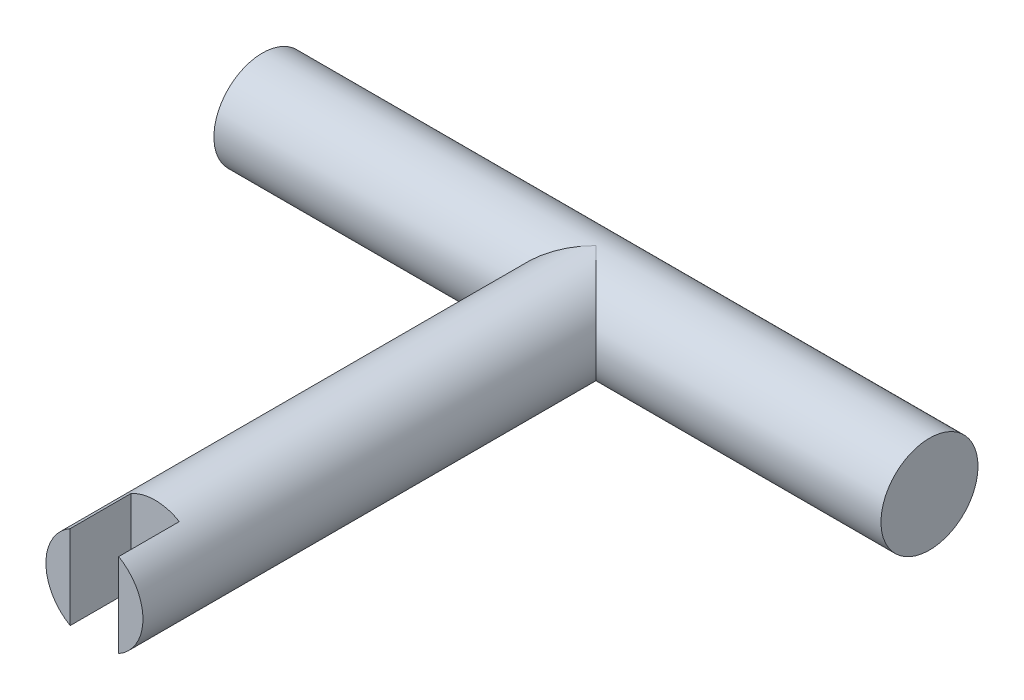
SolidWorks part; units mm, degrees
ref_plane "Front Plane" through (0, 0, 0) normal (0, 0, 1) x (1, 0, 0)
ref_plane "Top Plane" through (0, 0, 0) normal (0, 1, 0) x (1, 0, 0)
ref_plane "Right Plane" through (0, 0, 0) normal (1, 0, 0) x (0, 0, -1)
sketch "LAYOUT" plane through (0, 0, 0) normal (0, 1, 0) x (1, 0, 0)
  line L0 (0, 0) -> (0, 141.5) construction
  line L1 (-18.6718, 141.5) -> (18.6718, 141.5) construction
  line L2 (0, 141.5) -> (0, 161.0961) construction
  line L3 (-15.8007, 105.15) -> (14.7476, 105.15) construction
  line L4 (-27.3866, 200) -> (27.4888, 200) construction
  point P7 (0, 141.5)
  dimension "D1" = 141.5
  dimension "D2" = 105.15
  dimension "D3" = 200
ref_axis "Axis1" through (0, 0, -169.1509) along (0, 0, 1)
ref_plane "Plane1" through (0, 0, -105.15) normal (0, 0, 1) x (1, 0, 0)
sketch "Sketch1" plane through (0, 0, -105.15) normal (0, 0, 1) x (1, 0, 0)
  circle A0 centre (0, 0) radius 4
  dimension "D1" = 8
extrude "Boss-Extrude2" add sketch "Sketch1" against normal up to vertex (36.35 mm away) up to point (0, 0, -141.5)
sketch "Sketch2" plane through (0, 0, -105.15) normal (0, 0, 1) x (1, 0, 0)
  line L0 (-2, 3.4641) -> (-2, -3.4641)
  line L1 (2, 3.4641) -> (2, -3.4641)
  circle A0 centre (0, 0) radius 4 construction
  arc A1 (2, -3.4641) -> (2, 3.4641) centre (0, 0) ccw
  arc A2 (-2, -3.4641) -> (2, -3.4641) centre (0, 0) ccw construction
  arc A3 (2, 3.4641) -> (-2, 3.4641) centre (0, 0) ccw construction
  arc A4 (-2, 3.4641) -> (-2, -3.4641) centre (0, 0) ccw
  dimension "D1" = 2
  dimension "D2" = 2
extrude "Boss-Extrude3" add sketch "Sketch2" along normal blind 5
sketch "Sketch3" plane through (0, 0, 0) normal (1, 0, 0) x (0, 0, -1)
  circle A0 centre (141.5, 0) radius 4
extrude "Boss-Extrude4" add sketch "Sketch3" along normal blind 27.5 and the other way blind 27.5
